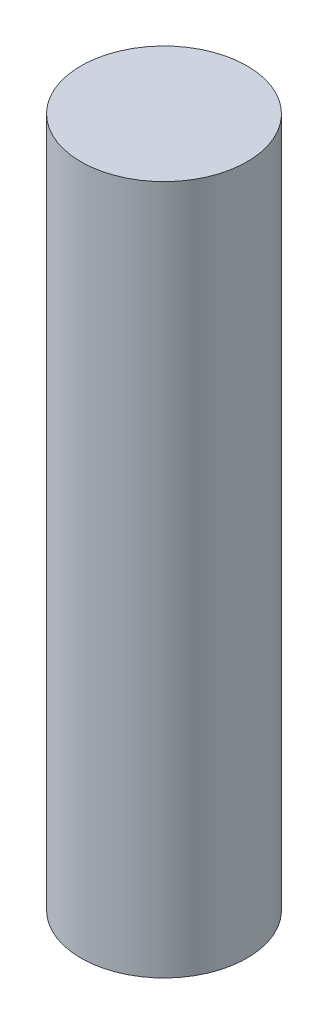
SolidWorks part; units mm, degrees
ref_plane "Plan de face" through (0, 0, 0) normal (0, 0, 1) x (1, 0, 0)
ref_plane "Plan de dessus" through (0, 0, 0) normal (0, 1, 0) x (1, 0, 0)
ref_plane "Plan de droite" through (0, 0, 0) normal (1, 0, 0) x (0, 0, -1)
sketch "Esquisse1" plane through (0, 0, 0) normal (0, 1, 0) x (1, 0, 0)
  circle A0 centre (0, 0) radius 3
  dimension "D1" = 6
extrude "Boss.-Extru.1" add sketch "Esquisse1" along normal blind 24.9
